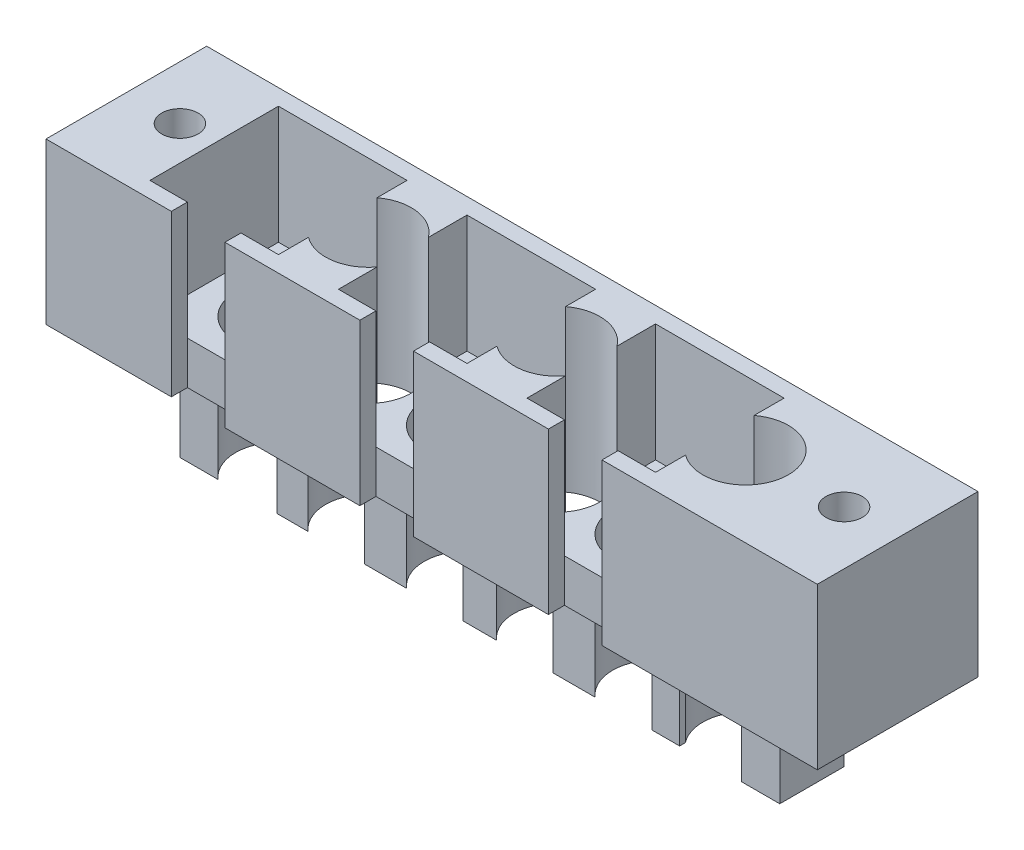
SolidWorks part; units mm, degrees
ref_plane "Front Plane" through (0, 0, 0) normal (0, 0, 1) x (1, 0, 0)
ref_plane "Top Plane" through (0, 0, 0) normal (0, 1, 0) x (1, 0, 0)
ref_plane "Right Plane" through (0, 0, 0) normal (1, 0, 0) x (0, 0, -1)
sketch "Sketch1" plane through (0, 0, 0) normal (0, 1, 0) x (1, 0, 0)
  line L0 (55.3347, -24.7724) -> (55.3347, -9.7724)
  line L1 (-16.6653, -9.7724) -> (55.3347, -9.7724)
  line L2 (55.3347, -24.7724) -> (-16.6653, -24.7724)
  line L3 (-4.9653, -23.7724) -> (-4.9653, -24.7724)
  line L4 (0.0347, -23.7724) -> (0.0347, -24.7724)
  line L5 (12.6347, -23.7724) -> (12.6347, -24.7724)
  line L6 (17.6347, -23.7724) -> (17.6347, -24.7724)
  line L7 (30.2347, -23.7724) -> (30.2347, -24.7724)
  line L8 (-16.6653, -9.7724) -> (-16.6653, -24.7724)
  line L9 (35.2347, -23.7724) -> (35.2347, -24.7724)
  line L10 (-11.6653, -4.2724) -> (-11.6653, -30.2724) construction
  line L11 (50.3347, -4.2724) -> (50.3347, -30.2724) construction
  line L12 (-16.6653, -17.2724) -> (50.3347, -17.2724) construction
  circle A0 centre (-11.6653, -17.2724) radius 1.7
  circle A1 centre (50.3347, -17.2724) radius 1.7
  line B0 (-8.4653, -11.2724) -> (-8.4653, -23.2724)
  line B1 (3.5347, -23.2724) -> (3.5347, -11.2724)
  line B2 (3.5347, -11.2724) -> (-8.4653, -11.2724)
  line B3 (-8.4653, -23.2724) -> (3.5347, -23.2724)
  line B4 (-8.4653, -11.2724) -> (3.5347, -23.2724) construction
  line B5 (-8.4653, -23.2724) -> (3.5347, -11.2724) construction
  line B6 (-2.4653, -11.2724) -> (-2.4653, -23.2724) construction
  line B7 (4.0347, -10.7724) -> (-8.9653, -10.7724)
  line B8 (-8.9653, -10.7724) -> (-8.9653, -23.7724)
  line B9 (4.0347, -23.7724) -> (4.0347, -10.7724)
  line B10 (-8.9653, -23.7724) -> (-4.9653, -23.7724)
  line B11 (4.0347, -23.7724) -> (0.0347, -23.7724)
  line B12 (-4.9653, -23.7724) -> (-4.9653, -23.2724)
  line B13 (0.0347, -23.7724) -> (0.0347, -23.2724)
  circle B14 centre (-2.4653, -17.2724) radius 4
  line B15 (9.1347, -11.2724) -> (9.1347, -23.2724)
  line B16 (21.1347, -23.2724) -> (21.1347, -11.2724)
  line B17 (21.1347, -11.2724) -> (9.1347, -11.2724)
  line B18 (9.1347, -23.2724) -> (21.1347, -23.2724)
  line B19 (9.1347, -11.2724) -> (21.1347, -23.2724) construction
  line B20 (9.1347, -23.2724) -> (21.1347, -11.2724) construction
  line B21 (15.1347, -11.2724) -> (15.1347, -23.2724) construction
  line B22 (21.6347, -10.7724) -> (8.6347, -10.7724)
  line B23 (8.6347, -10.7724) -> (8.6347, -23.7724)
  line B24 (21.6347, -23.7724) -> (21.6347, -10.7724)
  line B25 (8.6347, -23.7724) -> (12.6347, -23.7724)
  line B26 (21.6347, -23.7724) -> (17.6347, -23.7724)
  line B27 (12.6347, -23.7724) -> (12.6347, -23.2724)
  line B28 (17.6347, -23.7724) -> (17.6347, -23.2724)
  circle B29 centre (15.1347, -17.2724) radius 4
  line B30 (26.7347, -11.2724) -> (26.7347, -23.2724)
  line B31 (38.7347, -23.2724) -> (38.7347, -11.2724)
  line B32 (38.7347, -11.2724) -> (26.7347, -11.2724)
  line B33 (26.7347, -23.2724) -> (38.7347, -23.2724)
  line B34 (26.7347, -11.2724) -> (38.7347, -23.2724) construction
  line B35 (26.7347, -23.2724) -> (38.7347, -11.2724) construction
  line B36 (32.7347, -11.2724) -> (32.7347, -23.2724) construction
  line B37 (39.2347, -10.7724) -> (26.2347, -10.7724)
  line B38 (26.2347, -10.7724) -> (26.2347, -23.7724)
  line B39 (39.2347, -23.7724) -> (39.2347, -10.7724)
  line B40 (26.2347, -23.7724) -> (30.2347, -23.7724)
  line B41 (39.2347, -23.7724) -> (35.2347, -23.7724)
  line B42 (30.2347, -23.7724) -> (30.2347, -23.2724)
  line B43 (35.2347, -23.7724) -> (35.2347, -23.2724)
  circle B44 centre (32.7347, -17.2724) radius 4
  dimension "D5" = 0
  dimension "D1" = 0
  dimension "D2" = 0
  dimension "D3" = 5
  dimension "D4" = 72
  dimension "D6" = 7.7
  dimension "D7" = 17.6
  dimension "D8" = 17.6
  dimension "D9" = 15
sketch_block_instance "Block10-1"
sketch_block "Block10" parameters "D1"=12
sketch_block_instance "Block10-2"
sketch_block_instance "Block10-3"
extrude "Boss-Extrude1" add sketch "Sketch1" along normal blind 4 contours B0 B3 B1 B2 B14 | B15 B18 B16 B17 B29 | B30 B33 B31 B32 B44 region at (32.7347, 0, 23.1026) region at (15.1347, 0, 23.1026) region at (-6.7153, 0, 23.1026)
extrude "Boss-Extrude2" add sketch "Sketch1<3>" along normal blind 15 contours L8 A0 | A1 | B13 B11 B9 B7 B8 B10 B12 B3 B0 B2 B1 | B28 B26 B24 B22 B23 B25 B27 B18 B15 B17 B16 | B43 B41 B39 B37 B38 B40 B42 B33 B30 B32 B31 region at (23.3959, 0, 17.0779) region at (35.4186, 0, 23.5224) region at (17.8186, 0, 23.5224) region at (-6.9653, 0, 23.5885)
sketch "Sketch1<3>" plane through (0, 0, 0) normal (0, 1, 0) x (1, 0, 0) same geometry as "Sketch1"
sketch "Sketch3" plane through (0, 0, 0) normal (0, -1, 0) x (1, 0, 0)
  text T0 "F12"
sketch "Sketch4" plane through (0, 15, 0) normal (0, 1, 0) x (1, 0, 0)
  line L0 (55.3347, -17.2724) -> (-16.6653, -17.2724) construction
  line L1 (55.3347, -24.7724) -> (55.3347, -9.7724) construction
  line L2 (-16.6653, -9.7724) -> (-16.6653, -24.7724) construction
  line L3 (-2.4653, -11.2724) -> (-2.4653, -23.2724) construction
  line L4 (3.5347, -11.2724) -> (-8.4653, -11.2724) construction
  line L5 (-4.9653, -23.2724) -> (0.0347, -23.2724) construction
  line L6 (15.1347, -11.2724) -> (15.1347, -23.2724) construction
  line L7 (21.1347, -11.2724) -> (9.1347, -11.2724) construction
  line L8 (12.6347, -23.2724) -> (17.6347, -23.2724) construction
  line L9 (32.7347, -11.2724) -> (32.7347, -23.2724) construction
  line L10 (38.7347, -11.2724) -> (26.7347, -11.2724) construction
  line L11 (30.2347, -23.2724) -> (35.2347, -23.2724) construction
  line L14 (3.4347, -10.7724) -> (3.4347, -9.7724)
  line L15 (-16.6653, -9.7724) -> (55.3347, -9.7724) construction
  line L16 (8.4347, -10.7724) -> (8.4347, -9.7724)
  line L17 (21.0347, -10.7724) -> (21.0347, -9.7724)
  line L18 (26.0347, -10.7724) -> (26.0347, -9.7724)
  line L19 (38.6347, -10.7724) -> (38.6347, -9.7724)
  line L20 (43.6347, -10.7724) -> (43.6347, -9.7724)
  line B0 (11.9347, -23.2724) -> (11.9347, -11.2724)
  line B1 (-0.0653, -11.2724) -> (-0.0653, -23.2724)
  line B2 (-0.0653, -23.2724) -> (11.9347, -23.2724)
  line B3 (11.9347, -11.2724) -> (-0.0653, -11.2724)
  line B4 (11.9347, -23.2724) -> (-0.0653, -11.2724) construction
  line B5 (11.9347, -11.2724) -> (-0.0653, -23.2724) construction
  line B6 (5.9347, -23.2724) -> (5.9347, -11.2724) construction
  line B7 (-0.5653, -23.7724) -> (12.4347, -23.7724)
  line B8 (12.4347, -23.7724) -> (12.4347, -10.7724)
  line B9 (-0.5653, -10.7724) -> (-0.5653, -23.7724)
  line B10 (12.4347, -10.7724) -> (8.4347, -10.7724)
  line B11 (-0.5653, -10.7724) -> (3.4347, -10.7724)
  line B12 (8.4347, -10.7724) -> (8.4347, -11.2724)
  line B13 (3.4347, -10.7724) -> (3.4347, -11.2724)
  circle B14 centre (5.9347, -17.2724) radius 4
  line B15 (29.5347, -23.2724) -> (29.5347, -11.2724)
  line B16 (17.5347, -11.2724) -> (17.5347, -23.2724)
  line B17 (17.5347, -23.2724) -> (29.5347, -23.2724)
  line B18 (29.5347, -11.2724) -> (17.5347, -11.2724)
  line B19 (29.5347, -23.2724) -> (17.5347, -11.2724) construction
  line B20 (29.5347, -11.2724) -> (17.5347, -23.2724) construction
  line B21 (23.5347, -23.2724) -> (23.5347, -11.2724) construction
  line B22 (17.0347, -23.7724) -> (30.0347, -23.7724)
  line B23 (30.0347, -23.7724) -> (30.0347, -10.7724)
  line B24 (17.0347, -10.7724) -> (17.0347, -23.7724)
  line B25 (30.0347, -10.7724) -> (26.0347, -10.7724)
  line B26 (17.0347, -10.7724) -> (21.0347, -10.7724)
  line B27 (26.0347, -10.7724) -> (26.0347, -11.2724)
  line B28 (21.0347, -10.7724) -> (21.0347, -11.2724)
  circle B29 centre (23.5347, -17.2724) radius 4
  line B30 (47.1347, -23.2724) -> (47.1347, -11.2724)
  line B31 (35.1347, -11.2724) -> (35.1347, -23.2724)
  line B32 (35.1347, -23.2724) -> (47.1347, -23.2724)
  line B33 (47.1347, -11.2724) -> (35.1347, -11.2724)
  line B34 (47.1347, -23.2724) -> (35.1347, -11.2724) construction
  line B35 (47.1347, -11.2724) -> (35.1347, -23.2724) construction
  line B36 (41.1347, -23.2724) -> (41.1347, -11.2724) construction
  line B37 (34.6347, -23.7724) -> (47.6347, -23.7724)
  line B38 (47.6347, -23.7724) -> (47.6347, -10.7724)
  line B39 (34.6347, -10.7724) -> (34.6347, -23.7724)
  line B40 (47.6347, -10.7724) -> (43.6347, -10.7724)
  line B41 (34.6347, -10.7724) -> (38.6347, -10.7724)
  line B42 (43.6347, -10.7724) -> (43.6347, -11.2724)
  line B43 (38.6347, -10.7724) -> (38.6347, -11.2724)
  circle B44 centre (41.1347, -17.2724) radius 4
  line M16 (3.5347, -11.2724) -> (3.5347, -23.2724)
  line M22 (9.1347, -23.2724) -> (9.1347, -11.2724)
  line M24 (21.1347, -11.2724) -> (21.1347, -23.2724)
  line M30 (26.7347, -23.2724) -> (26.7347, -11.2724)
  line M32 (38.7347, -11.2724) -> (38.7347, -23.2724)
  dimension "D1" = 0
  dimension "D2" = 0
  dimension "D3" = 0
  dimension "D4" = 8.4
  dimension "D5" = 8.4
  dimension "D6" = 8.4
  dimension "D7" = 14.2
  dimension "D8" = 14.2
sketch_block_instance "Block10-5"
sketch_block_instance "Block10-6"
sketch_block_instance "Block10-7"
extrude "Cut-Extrude1" cut sketch "Sketch4" against normal through all contours B14 M22 M16 | B29 M30 M24 | B44 M32 | B14 M16 | B14 M22 | B29 M24 | B29 M30 | B44 M32 region at (9.4576, 15, 17.2724) region at (6.2466, 15, 17.2724) region at (2.8823, 15, 17.2724) region at (27.0576, 15, 17.2724) region at (23.8466, 15, 17.2724) region at (20.4823, 15, 17.2724) region at (41.6415, 15, 17.2724) region at (38.0823, 15, 17.2724)
sketch "Sketch5" plane through (0, 0, 0) normal (0, -1, 0) x (1, 0, 0)
  line L0 (0.4062, 14.4876) -> (0.4062, 14.2724)
  line L1 (0.4062, 20.2724) -> (37.9809, 20.2724)
  line L5 (0.4062, 20.2724) -> (0.4062, 14.4876)
  line L23 (37.9809, 14.2724) -> (37.9809, 20.2724)
  line L26 (37.9809, 14.2724) -> (0.4062, 14.2724)
  line L27 (-4.4006, 20.773) -> (-4.4006, 20.2724)
  line L28 (-4.4006, 20.2724) -> (-8.6681, 20.2724)
  line L29 (-8.6681, 20.2724) -> (-8.6681, 14.2724)
  line L30 (-8.6681, 14.2724) -> (-4.4006, 14.2724)
  line L31 (-4.4006, 14.2724) -> (-4.4006, 20.773)
  line L32 (-16.6653, 17.2724) -> (55.3347, 17.2724) construction
  line L33 (-16.6653, 9.7724) -> (-16.6653, 24.7724) construction
  line L34 (55.3347, 24.7724) -> (55.3347, 9.7724) construction
  line L35 (47.3304, 17.2724) -> (47.3304, 20.2724)
  line L39 (47.3304, 14.2724) -> (47.3304, 17.2724)
  line L41 (44.3347, 14.2724) -> (47.3304, 14.2724)
  line L42 (47.3304, 20.2724) -> (44.3347, 20.2724)
  line L43 (44.3347, 14.2724) -> (42.2928, 14.2724)
  line L44 (42.2928, 14.2724) -> (42.2928, 20.2724)
  line L45 (42.2928, 20.2724) -> (44.3347, 20.2724)
  line L46 (-2.4653, 21.2724) -> (-2.4653, 13.2724) construction
  line L47 (41.1347, 21.2724) -> (41.1347, 13.2724) construction
  circle A0 centre (-2.4653, 17.2724) radius 4 construction
  circle A1 centre (5.9347, 17.2724) radius 4
  circle A2 centre (-2.4653, 17.2724) radius 4
  circle A3 centre (15.1347, 17.2724) radius 4
  circle A4 centre (23.5347, 17.2724) radius 4
  circle A5 centre (32.7347, 17.2724) radius 4
  circle A6 centre (41.1347, 17.2724) radius 4
  circle M18 centre (5.9347, 17.2724) radius 4
  circle M19 centre (23.5347, 17.2724) radius 4
  circle M20 centre (41.1347, 17.2724) radius 4
  circle M37 centre (-2.4653, 17.2724) radius 4
  circle M40 centre (15.1347, 17.2724) radius 4
  circle M41 centre (32.7347, 17.2724) radius 4
  dimension "D1" = 6
  dimension "D2" = 3
  dimension "D3" = 6
  dimension "D4" = 3
  dimension "D5" = 14.2
  dimension "D6" = 14.2
extrude "Cut-Extrude2" cut sketch "Sketch3" against normal blind 1
extrude "Boss-Extrude4" add sketch "Sketch5" along normal blind 9 contours L29 L30 L28 M37 | L26 L1 L5 L0 M18 M37 | L26 L1 M40 M18 | L26 L1 M19 M40 | L26 L1 M41 M19 | L26 L23 L1 M20 M41 | L45 L43 L41 L39 L35 L42 M20 region at (1.7438, 0, 17.2724) region at (-7.3298, 0, 17.2724) region at (10.5347, 0, 17.2724) region at (19.3347, 0, 17.2724) region at (28.1347, 0, 17.2724) region at (36.8911, 0, 17.2724) region at (45.9956, 0, 17.2724)
